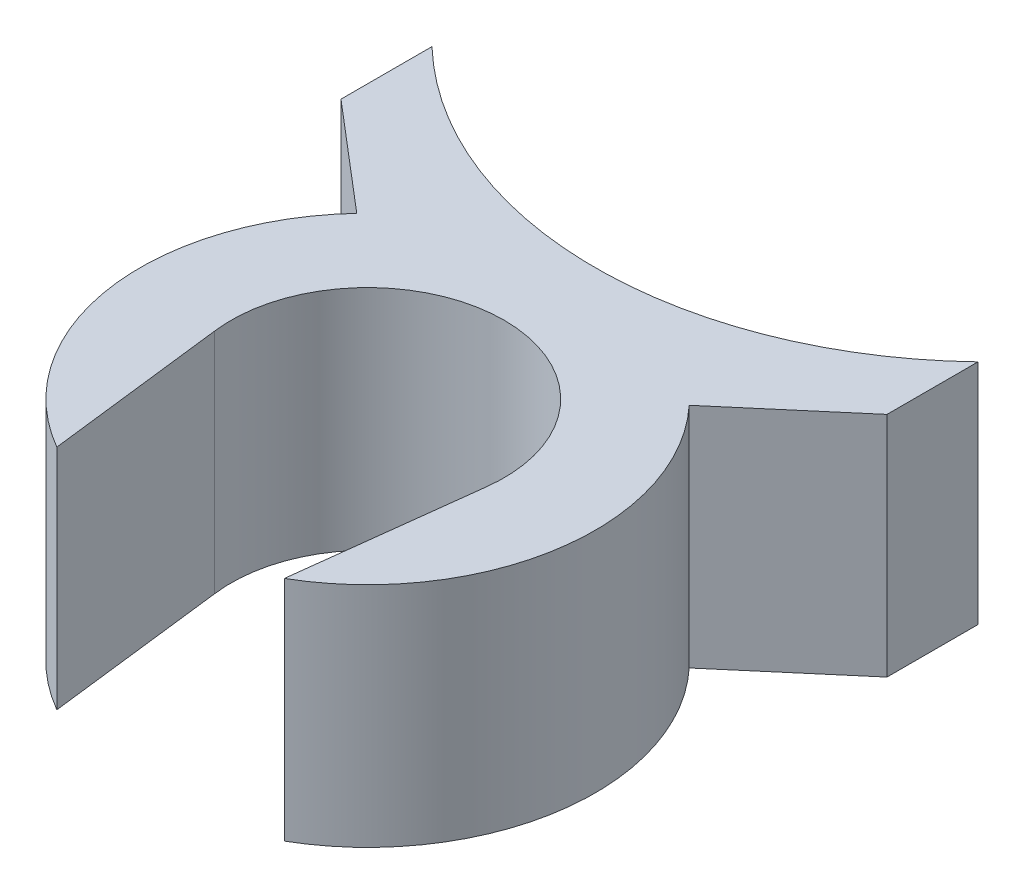
SolidWorks part; units mm, degrees
ref_plane "Front" through (0, 0, 0) normal (0, 0, 1) x (1, 0, 0)
ref_plane "Top" through (0, 0, 0) normal (0, 1, 0) x (1, 0, 0)
ref_plane "Right" through (0, 0, 0) normal (1, 0, 0) x (0, 0, -1)
sketch "Croquis1" plane through (0, 0, 0) normal (0, 1, 0) x (1, 0, 0)
  line L0 (0, 0) -> (0, 7) construction
  line L2 (-6, 7.4139) -> (-6, 3.4139)
  line L3 (-6, 3.4139) -> (-3.6531, 3.4139)
  line L4 (6, 7.4139) -> (6, 3.4139)
  line L5 (3.6531, 3.4139) -> (6, 3.4139)
  circle A0 centre (0, 0) radius 3
  arc A1 (-3.6531, 3.4139) -> (3.6531, 3.4139) centre (0, 0) ccw
  arc A2 (-6, 7.4139) -> (6, 7.4139) centre (0, 13.6636) ccw
  dimension "D1" = 6
  dimension "D2" = 10
  dimension "D3" = 7
  dimension "D4" = 4
  dimension "D5" = 6
  dimension "D6" = 12
extrude "Saliente-Extruir1" add sketch "Croquis1" along normal blind 5
sketch "Croquis2" plane through (0, 5, 0) normal (0, 1, 0) x (1, 0, 0)
  line L0 (0, 0) -> (0, -5) construction
  line L1 (-2.5, -4.3301) -> (-2.9818, -0.3301)
  line L2 (2.5, -4.3301) -> (2.9818, -0.3301)
  arc A0 (-3.6531, 3.4139) -> (3.6531, 3.4139) centre (0, 0) ccw construction
  circle A1 centre (0, 0) radius 3 construction
  arc A2 (-2.9818, -0.3301) -> (2.9818, -0.3301) centre (0, 0) ccw
  arc A3 (-2.5, -4.3301) -> (3.6531, 3.4139) centre (0, 0) ccw
  arc M7 (-3.6531, 3.4139) -> (3.6531, 3.4139) centre (0, 0) ccw
  circle M10 centre (0, 0) radius 3
  dimension "D1" = 2.5
  dimension "D2" = 4
extrude "Cortar-Extruir1" cut sketch "Croquis2" against normal blind 10 contours L0 A3 L2 M10 | L0 A2 L1 M7 region at (0, 5, 1.0557)
sketch "Croquis3" plane through (0, 5, 0) normal (0, 1, 0) x (1, 0, 0)
  line L0 (3.6531, 3.4139) -> (6, 5.4139)
  line L1 (6, 3.4139) -> (6, 7.4139) construction
  line L2 (0, 3) -> (0, 5) construction
  line L3 (-3.6531, 3.4139) -> (-6, 5.4139)
  line L4 (3.6531, 3.4139) -> (6, 3.4139) construction
  line L5 (-6, 3.4139) -> (-3.6531, 3.4139) construction
  line L6 (-6, 7.4139) -> (-6, 3.4139) construction
  line L7 (6, 3.4139) -> (6, 5.4139)
  line L8 (3.6531, 3.4139) -> (6, 3.4139)
  line L9 (-6, 3.4139) -> (-3.6531, 3.4139)
  line L10 (-6, 5.4139) -> (-6, 3.4139)
  arc A0 (2.9749, -0.3873) -> (-2.9749, -0.3873) centre (0, 0) ccw construction
  arc A1 (-6, 7.4139) -> (6, 7.4139) centre (0, 13.6636) ccw construction
  point P2 (5, 4.7321)
  point P4 (0, 0)
  point P15 (6, 5.8267)
  dimension "D1" = 2
extrude "Cortar-Extruir2" cut sketch "Croquis3" against normal blind 10
